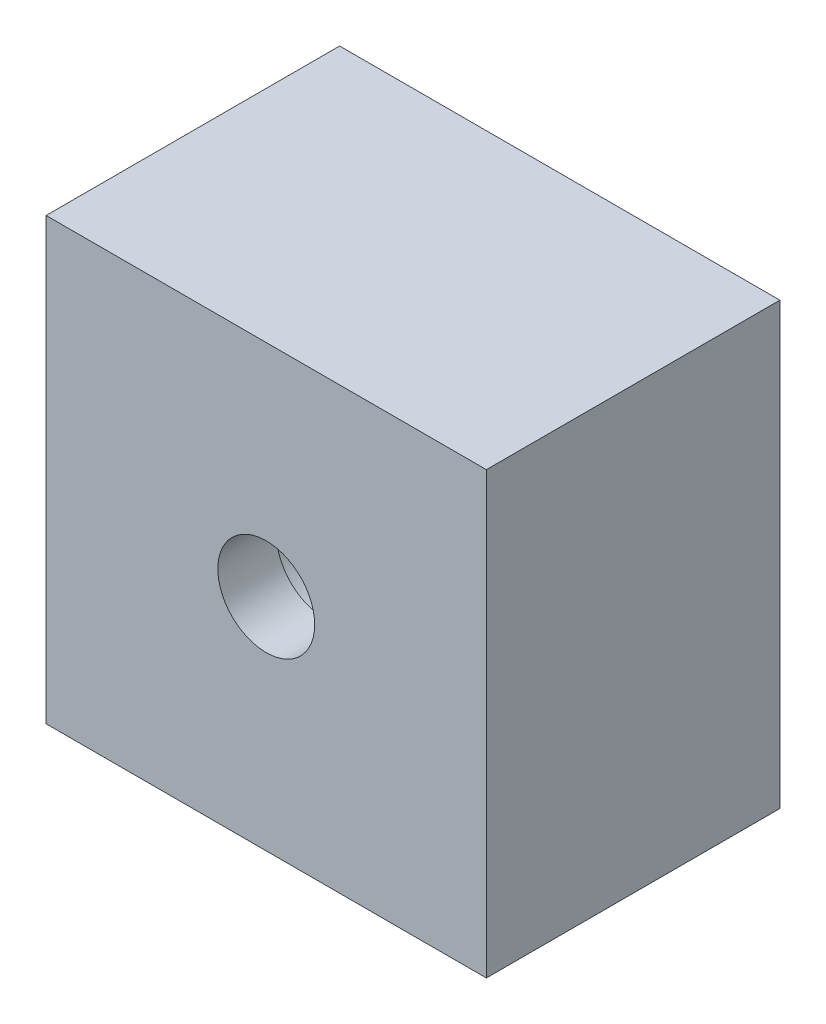
SolidWorks part; units mm, degrees
ref_plane "Front Plane" through (0, 0, 0) normal (0, 0, 1) x (1, 0, 0)
ref_plane "Top Plane" through (0, 0, 0) normal (0, 1, 0) x (1, 0, 0)
ref_plane "Right Plane" through (0, 0, 0) normal (1, 0, 0) x (0, 0, -1)
sketch "Sketch1" plane through (0, 0, 0) normal (0, 0, 1) x (1, 0, 0)
  line L1 (7.5, 7.5) -> (-7.5, 7.5)
  line L2 (7.5, 7.5) -> (7.5, -7.5)
  line L3 (7.5, -7.5) -> (-7.5, -7.5)
  line L4 (-7.5, 7.5) -> (-7.5, -7.5)
  line L5 (7.5, 7.5) -> (-7.5, -7.5) construction
  line L6 (7.5, -7.5) -> (-7.5, 7.5) construction
  line L12 (0, 0) -> (-5.3234, 0) construction
  line L19 (0, -2.44) -> (0, 1.51) construction
  circle A0 centre (0, 0) radius 1.65
  circle A1 centre (0, 0) radius 2.45
  circle A2 centre (0, 0) radius 11.75 construction
  circle A3 centre (0, 0) radius 5
  dimension "D1" = 4.9
  dimension "D2" = 3.3
  dimension "D4" = 23.5
  dimension "D9" = 10
  dimension "D3" = 15
  dimension "D7" = 15
extrude "Boss-Extrude4" add sketch "Sketch1" along normal blind 10 contours L1 L4 L3 L2 A3 | A3 A1 | A1 A0 region at (7.2879, 0, 0) region at (-2.3807, 0, 0) region at (-4.8586, 0, 0)
extrude "Cut-Extrude3" cut sketch "Sketch1<9>" along normal blind 8 contours A1 A0 region at (-2.3807, 0, 0)
sketch "Sketch1<9>" plane through (0, 0, 0) normal (0, 0, 1) x (1, 0, 0) same geometry as "Sketch1"
